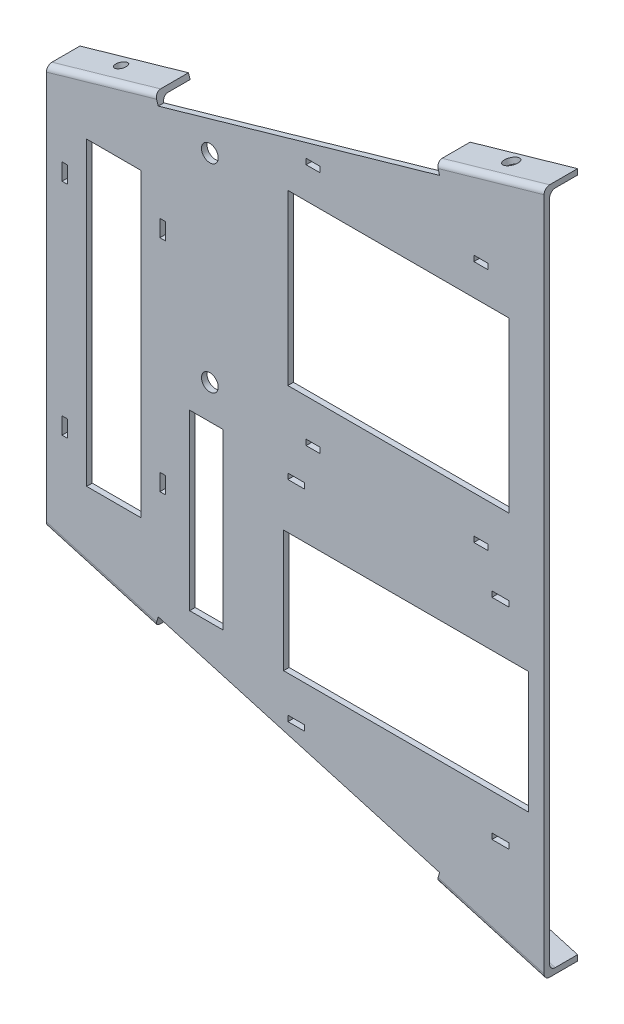
SolidWorks part; units mm, degrees
material "6061 Alloy"
ref_plane "Płaszczyzna XY" through (0, 0, 0) normal (0, 0, 1) x (1, 0, 0)
ref_plane "Płaszczyzna XZ" through (0, 0, 0) normal (0, 1, 0) x (1, 0, 0)
ref_plane "Płaszczyzna YZ" through (0, 0, 0) normal (1, 0, 0) x (0, 0, -1)
sketch "Sketch1" plane through (0, 0, 0) normal (0, 0, 1) x (1, 0, 0)
  line L0 (-10.9048, -82.7238) -> (167.0952, -133.7453) construction
  line L1 (-10.9048, 82.7238) -> (167.0952, 133.7453) construction
  line L2 (-299.5051, 0) -> (299.5051, 0) construction
  line L3 (-10.9048, -69.7204) -> (-10.9048, 69.7204)
  line L4 (167.0952, -120.7419) -> (167.0952, 120.7419)
  line L5 (-10.9048, 69.7204) -> (167.0952, 120.7419)
  line L6 (167.0952, -120.7419) -> (-10.9048, -69.7204)
  point P6 (-10.9048, 0)
extrude "Boss-Extrude1" add sketch "Sketch1" along normal blind 2
sketch "Sketch2" plane through (0, 0, 2) normal (0, 0, 1) x (1, 0, 0)
  line L0 (13.1875, -57.6943) -> (13.1875, 61.3057) construction
  line L1 (29.6875, 38.6369) -> (31.6875, 38.6369)
  line L2 (29.6875, 38.6369) -> (29.6875, 44.6369)
  line L3 (29.6875, 44.6369) -> (31.6875, 44.6369)
  line L4 (29.6875, 32.3057) -> (29.6875, 52.3057) construction
  line L5 (31.6875, 38.6369) -> (31.6875, 44.6369)
  line L6 (-3.3125, 2.3057) -> (29.6875, 2.3057) construction
  line L7 (31.6875, -34.0255) -> (31.6875, -40.0255)
  line L8 (161.9963, 2.39) -> (161.9963, 87.39)
  line L9 (66.9963, 2.39) -> (161.9963, 2.39)
  line L10 (66.9963, 87.39) -> (66.9963, 2.39)
  line L11 (161.9963, 87.39) -> (66.9963, 87.39)
  line L12 (161.9963, 2.39) -> (161.9963, 87.39) construction
  line L13 (66.9963, 2.39) -> (161.9963, 2.39) construction
  line L14 (66.9963, 87.39) -> (66.9963, 2.39) construction
  line L15 (161.9963, 87.39) -> (66.9963, 87.39) construction
  line L16 (161.4673, -13.3702) -> (68.4673, -13.3702)
  line L17 (166.4673, -81.3702) -> (166.4673, -18.3702)
  line L18 (68.4673, -86.3702) -> (161.4673, -86.3702)
  line L19 (63.4673, -18.3702) -> (63.4673, -81.3702)
  line L20 (161.4673, -13.3702) -> (68.4673, -13.3702) construction
  line L21 (166.4673, -81.3702) -> (166.4673, -18.3702) construction
  line L22 (68.4673, -86.3702) -> (161.4673, -86.3702) construction
  line L23 (63.4673, -18.3702) -> (63.4673, -81.3702) construction
  line L24 (-3.3125, 32.3057) -> (-3.3125, -27.6943)
  line L25 (29.6875, 32.3057) -> (-3.3125, 32.3057)
  line L26 (29.6875, -27.6943) -> (29.6875, 32.3057)
  line L27 (-3.3125, -27.6943) -> (29.6875, -27.6943)
  line L28 (-3.3125, 32.3057) -> (-3.3125, -27.6943) construction
  line L29 (29.6875, 32.3057) -> (-3.3125, 32.3057) construction
  line L30 (29.6875, -27.6943) -> (29.6875, 32.3057) construction
  line L31 (-3.3125, -27.6943) -> (29.6875, -27.6943) construction
  line L32 (27.6875, 61.3057) -> (-1.3125, 61.3057)
  line L33 (29.6875, 52.3057) -> (29.6875, 59.3057)
  line L34 (-3.3125, 52.3057) -> (29.6875, 52.3057)
  line L35 (-3.3125, 59.3057) -> (-3.3125, 52.3057)
  line L36 (27.6875, 61.3057) -> (-1.3125, 61.3057) construction
  line L37 (29.6875, 52.3057) -> (29.6875, 59.3057) construction
  line L38 (-3.3125, 52.3057) -> (29.6875, 52.3057) construction
  line L39 (-3.3125, 59.3057) -> (-3.3125, 52.3057) construction
  line L40 (-1.3125, -57.6943) -> (27.6875, -57.6943)
  line L41 (-3.3125, -47.6943) -> (-3.3125, -55.6943)
  line L42 (29.6875, -47.6943) -> (-3.3125, -47.6943)
  line L43 (29.6875, -55.6943) -> (29.6875, -47.6943)
  line L44 (-1.3125, -57.6943) -> (27.6875, -57.6943) construction
  line L45 (-3.3125, -47.6943) -> (-3.3125, -55.6943) construction
  line L46 (29.6875, -47.6943) -> (-3.3125, -47.6943) construction
  line L47 (29.6875, -55.6943) -> (29.6875, -47.6943) construction
  line L48 (29.6875, -34.0255) -> (31.6875, -34.0255)
  line L49 (29.6875, -34.0255) -> (29.6875, -40.0255)
  line L50 (29.6875, -40.0255) -> (31.6875, -40.0255)
  line L51 (-3.3125, 44.6369) -> (-5.3125, 44.6369)
  line L52 (-3.3125, 38.6369) -> (-3.3125, 44.6369)
  line L53 (-3.3125, 38.6369) -> (-5.3125, 38.6369)
  line L54 (-5.3125, 38.6369) -> (-5.3125, 44.6369)
  line L55 (-3.3125, -34.0255) -> (-5.3125, -34.0255)
  line L56 (-5.3125, -34.0255) -> (-5.3125, -40.0255)
  line L57 (-3.3125, -40.0255) -> (-5.3125, -40.0255)
  line L58 (-3.3125, -34.0255) -> (-3.3125, -40.0255)
  line L59 (78.4673, -64.5246) -> (78.4673, -86.3702) construction
  line L60 (3.485, -51.4878) -> (22.8899, -51.4878)
  line L61 (3.485, -51.4878) -> (3.485, 56.0992)
  line L62 (3.485, 56.0992) -> (22.8899, 56.0992)
  line L63 (22.8899, -51.4878) -> (22.8899, 56.0992)
  line L64 (3.485, -51.4878) -> (22.8899, 56.0992) construction
  line L65 (3.485, 56.0992) -> (22.8899, -51.4878) construction
  line L66 (40.3295, -71.5793) -> (52.3295, -71.5793)
  line L67 (40.3295, -71.5793) -> (40.3295, -9.4599)
  line L68 (40.3295, -9.4599) -> (52.3295, -9.4599)
  line L69 (52.3295, -71.5793) -> (52.3295, -9.4599)
  line L70 (40.3295, -71.5793) -> (52.3295, -9.4599) construction
  line L71 (40.3295, -9.4599) -> (52.3295, -71.5793) construction
  line L72 (75.4673, -86.3702) -> (81.4673, -86.3702)
  line L73 (75.4673, -86.3702) -> (75.4673, -88.3702)
  line L74 (75.4673, -88.3702) -> (81.4673, -88.3702)
  line L75 (75.4673, -64.5246) -> (81.4673, -64.5246)
  line L76 (75.4673, -34.5246) -> (75.4673, -64.5246)
  line L77 (81.4673, -34.5246) -> (75.4673, -34.5246)
  line L78 (81.4673, -64.5246) -> (81.4673, -34.5246)
  line L79 (75.4673, -64.5246) -> (81.4673, -64.5246) construction
  line L80 (75.4673, -34.5246) -> (75.4673, -64.5246) construction
  line L81 (81.4673, -34.5246) -> (75.4673, -34.5246) construction
  line L82 (81.4673, -64.5246) -> (81.4673, -34.5246) construction
  line L83 (148.4673, -34.5246) -> (148.4673, -64.5246)
  line L84 (154.4673, -34.5246) -> (148.4673, -34.5246)
  line L85 (154.4673, -64.5246) -> (154.4673, -34.5246)
  line L86 (148.4673, -64.5246) -> (154.4673, -64.5246)
  line L87 (148.4673, -34.5246) -> (148.4673, -64.5246) construction
  line L88 (154.4673, -34.5246) -> (148.4673, -34.5246) construction
  line L89 (154.4673, -64.5246) -> (154.4673, -34.5246) construction
  line L90 (148.4673, -64.5246) -> (154.4673, -64.5246) construction
  line L91 (147.4963, 27.4636) -> (147.4963, 62.3163)
  line L92 (141.4963, 27.4636) -> (147.4963, 27.4636)
  line L93 (141.4963, 62.3163) -> (141.4963, 27.4636)
  line L94 (147.4963, 62.3163) -> (141.4963, 62.3163)
  line L95 (147.4963, 27.4636) -> (147.4963, 62.3163) construction
  line L96 (141.4963, 27.4636) -> (147.4963, 27.4636) construction
  line L97 (141.4963, 62.3163) -> (141.4963, 27.4636) construction
  line L98 (147.4963, 62.3163) -> (141.4963, 62.3163) construction
  line L99 (87.4963, 62.3163) -> (81.4963, 62.3163)
  line L100 (87.4963, 27.4636) -> (87.4963, 62.3163)
  line L101 (81.4963, 27.4636) -> (87.4963, 27.4636)
  line L102 (81.4963, 62.3163) -> (81.4963, 27.4636)
  line L103 (87.4963, 62.3163) -> (81.4963, 62.3163) construction
  line L104 (87.4963, 27.4636) -> (87.4963, 62.3163) construction
  line L105 (81.4963, 27.4636) -> (87.4963, 27.4636) construction
  line L106 (81.4963, 62.3163) -> (81.4963, 27.4636) construction
  line L107 (81.4673, -88.3702) -> (81.4673, -86.3702)
  line L108 (63.4673, -49.8702) -> (166.4673, -49.8702) construction
  line L109 (114.9673, -86.3702) -> (114.9673, -13.3702) construction
  line L110 (75.4673, -13.3702) -> (75.4673, -11.3702)
  line L111 (75.4673, -11.3702) -> (81.4673, -11.3702)
  line L112 (75.4673, -13.3702) -> (81.4673, -13.3702)
  line L113 (81.4673, -11.3702) -> (81.4673, -13.3702)
  line L114 (148.4673, -88.3702) -> (148.4673, -86.3702)
  line L115 (154.4673, -88.3702) -> (148.4673, -88.3702)
  line L116 (154.4673, -86.3702) -> (154.4673, -88.3702)
  line L117 (154.4673, -86.3702) -> (148.4673, -86.3702)
  line L118 (148.4673, -11.3702) -> (148.4673, -13.3702)
  line L119 (154.4673, -13.3702) -> (148.4673, -13.3702)
  line L120 (154.4673, -11.3702) -> (148.4673, -11.3702)
  line L121 (154.4673, -13.3702) -> (154.4673, -11.3702)
  line L122 (86.9963, 0.39) -> (86.9963, 2.39)
  line L123 (86.9963, 0.39) -> (81.9963, 0.39)
  line L124 (86.9963, 2.39) -> (81.9963, 2.39)
  line L125 (81.9963, 0.39) -> (81.9963, 2.39)
  line L126 (86.9963, 0.39) -> (81.9963, 2.39) construction
  line L127 (86.9963, 2.39) -> (81.9963, 0.39) construction
  line L128 (66.9963, 44.89) -> (161.9963, 44.89) construction
  line L129 (114.4963, 2.39) -> (114.4963, 87.39) construction
  line L130 (81.9963, 89.39) -> (81.9963, 87.39)
  line L131 (86.9963, 89.39) -> (81.9963, 89.39)
  line L132 (86.9963, 87.39) -> (81.9963, 87.39)
  line L133 (86.9963, 89.39) -> (86.9963, 87.39)
  line L134 (141.9963, 89.39) -> (141.9963, 87.39)
  line L135 (141.9963, 87.39) -> (146.9963, 87.39)
  line L136 (141.9963, 89.39) -> (146.9963, 89.39)
  line L137 (146.9963, 89.39) -> (146.9963, 87.39)
  line L138 (141.9963, 2.39) -> (146.9963, 0.39) construction
  line L139 (141.9963, 0.39) -> (146.9963, 2.39) construction
  line L140 (146.9963, 0.39) -> (146.9963, 2.39)
  line L141 (141.9963, 2.39) -> (146.9963, 2.39)
  line L142 (141.9963, 0.39) -> (146.9963, 0.39)
  line L143 (141.9963, 0.39) -> (141.9963, 2.39)
  line L144 (-10.9048, 69.7204) -> (-10.9048, -69.7204) construction
  line L146 (73.9192, -73.3653) -> (161.4673, -73.3653)
  line L147 (73.9192, -73.3653) -> (73.9192, -29.7941)
  line L148 (73.9192, -29.7941) -> (161.4673, -29.7941)
  line L149 (161.4673, -73.3653) -> (161.4673, -29.7941)
  line L150 (75.4673, 15.7339) -> (154.4673, 15.7339)
  line L151 (75.4673, 15.7339) -> (75.4673, 76.1907)
  line L152 (75.4673, 76.1907) -> (154.4673, 76.1907)
  line L153 (154.4673, 15.7339) -> (154.4673, 76.1907)
  circle A0 centre (47.5637, 2.7699) radius 3 construction
  circle A1 centre (47.5637, 73.7699) radius 3 construction
  arc A2 (29.6875, 59.3057) -> (27.6875, 61.3057) centre (27.6875, 59.3057) ccw
  arc A3 (-1.3125, 61.3057) -> (-3.3125, 59.3057) centre (-1.3125, 59.3057) ccw
  arc A4 (166.4673, -18.3702) -> (161.4673, -13.3702) centre (161.4673, -18.3702) ccw
  arc A5 (161.4673, -86.3702) -> (166.4673, -81.3702) centre (161.4673, -81.3702) ccw
  arc A6 (63.4673, -81.3702) -> (68.4673, -86.3702) centre (68.4673, -81.3702) ccw
  arc A7 (68.4673, -13.3702) -> (63.4673, -18.3702) centre (68.4673, -18.3702) ccw
  arc A8 (166.4673, -18.3702) -> (161.4673, -13.3702) centre (161.4673, -18.3702) ccw construction
  arc A9 (161.4673, -86.3702) -> (166.4673, -81.3702) centre (161.4673, -81.3702) ccw construction
  arc A10 (63.4673, -81.3702) -> (68.4673, -86.3702) centre (68.4673, -81.3702) ccw construction
  arc A11 (68.4673, -13.3702) -> (63.4673, -18.3702) centre (68.4673, -18.3702) ccw construction
  arc A12 (29.6875, 59.3057) -> (27.6875, 61.3057) centre (27.6875, 59.3057) ccw construction
  arc A13 (-1.3125, 61.3057) -> (-3.3125, 59.3057) centre (-1.3125, 59.3057) ccw construction
  arc A14 (-3.3125, -55.6943) -> (-1.3125, -57.6943) centre (-1.3125, -55.6943) ccw
  arc A15 (27.6875, -57.6943) -> (29.6875, -55.6943) centre (27.6875, -55.6943) ccw
  arc A16 (-3.3125, -55.6943) -> (-1.3125, -57.6943) centre (-1.3125, -55.6943) ccw construction
  arc A17 (27.6875, -57.6943) -> (29.6875, -55.6943) centre (27.6875, -55.6943) ccw construction
  circle A18 centre (47.5637, 2.7699) radius 3
  circle A19 centre (47.5637, 73.7699) radius 3
  point P44 (45.9552, 2.3057)
  point P57 (13.1875, 2.3057)
  point P84 (78.4673, -64.5246)
  point P87 (78.4673, -86.3702)
  point P102 (151.4673, -86.3702)
  point P107 (84.4963, 2.39)
  point P109 (84.4963, 27.4636)
  point P142 (46.3295, -9.4599)
  dimension "D6" = 2
  dimension "D7" = 6
  dimension "D12" = 6
  dimension "D13" = 2
  dimension "D14" = 2
  dimension "D15" = 5
  dimension "D16" = 10.6421
  dimension "D17" = 12
  dimension "D18" = 48.2344
  dimension "D19" = 13.885
  dimension "D1" = 0
  dimension "D2" = 0
  dimension "D3" = 0
  dimension "D4" = 0
  dimension "D5" = 0
  dimension "D8" = 0
  dimension "D9" = 0
  dimension "D10" = 0
  dimension "D11" = 0
extrude "Cut-Extrude1" cut sketch "Sketch2" against normal blind 10
sketch "Sketch3" plane through (0, 0, 0) normal (0, 0, -1) x (-1, 0, 0)
  line L0 (10.9048, -69.7204) -> (-167.0952, -120.7419) construction
  line L1 (10.9048, -69.7204) -> (-167.0952, -120.7419)
  line L2 (10.9048, -69.7204) -> (10.9048, -71.7204)
  line L3 (10.9048, 69.7204) -> (10.9048, -69.7204) construction
  line L4 (-167.0952, -120.7419) -> (-167.0952, -122.7419)
  line L5 (-167.0952, -122.7419) -> (10.9048, -71.7204)
  line L6 (-167.0952, -120.7419) -> (-167.0952, 120.7419) construction
  line L7 (1.1, 0) -> (-1.1, 0) construction
  line L8 (-167.0952, 120.7419) -> (-167.0952, 122.7419)
  line L9 (-167.0952, 122.7419) -> (10.9048, 71.7204)
  line L10 (10.9048, 69.7204) -> (10.9048, 71.7204)
  line L11 (10.9048, 69.7204) -> (-167.0952, 120.7419)
  dimension "D1" = 2
  dimension "D2" = 2
extrude "Boss-Extrude2" add sketch "Sketch3" along normal blind 10 and the other way blind 2
fillet "Fillet1" radius 2 4 edges at (78.0952, 95.2312, 0) (78.0952, -95.2312, 0) (78.0952, -97.2312, 2) (78.0952, 97.2312, 2)
sketch "Sketch4" plane through (0, 0, 0) normal (0, 0, -1) x (-1, 0, 0)
  line L0 (10.9048, 67.6399) -> (-167.0952, 118.6614) construction
  line L1 (-29.0952, 79.1054) -> (-127.0952, 107.1959)
  line L3 (-124.8909, 114.8862) -> (-26.8909, 86.1054)
  line L4 (-26.8909, 86.1054) -> (-29.0952, 79.1054)
  line L5 (10.9048, 67.6399) -> (10.9048, -67.6399) construction
  line L11 (-128.0926, 113.6428) -> (-128.6437, 111.7203) construction
  line L12 (-128.0926, 113.6428) -> (-128.6437, 111.7203)
  line L13 (-128.6437, 111.7203) -> (-129.7245, 107.9495)
  line L14 (-127.0952, 107.1959) -> (-129.7245, 107.9495)
  line L15 (-124.8909, 114.8862) -> (-127.5153, 115.6569)
  line L16 (-128.0926, 113.6428) -> (-127.5153, 115.6569)
  line L18 (6.6, 0) -> (-6.6, 0) construction
  line L19 (-127.0952, -107.1959) -> (-129.7245, -107.9495)
  line L20 (-128.6437, -111.7203) -> (-129.7245, -107.9495)
  line L21 (-128.0926, -113.6428) -> (-128.6437, -111.7203)
  line L22 (-128.0926, -113.6428) -> (-127.5153, -115.6569)
  line L23 (-124.8909, -114.8862) -> (-127.5153, -115.6569)
  line L24 (-124.8909, -114.8862) -> (-26.8909, -86.1054)
  line L25 (-29.0952, -79.1054) -> (-127.0952, -107.1959)
  line L26 (-26.8909, -86.1054) -> (-29.0952, -79.1054)
  dimension "D1" = 40
  dimension "D2" = 40
  dimension "D3" = 8
  dimension "D4" = 7
  dimension "D5" = 179.628
  dimension "D6" = 271.113
extrude "Cut-Extrude2" cut sketch "Sketch4" against normal blind 10 and the other way blind 10
sketch "Sketch5" plane through (-19.2951, -67.3154, 0) normal (0.2755, 0.9613, 0) x (0.9613, -0.2755, 0)
  line L0 (154.4473, 10) -> (193.8963, 10) construction
  line L1 (193.8963, 2) -> (193.8963, 10) construction
  line L2 (8.7282, 10) -> (49.7139, 10) construction
  line L3 (8.7282, 2) -> (8.7282, 10) construction
  circle A0 centre (173.8963, 6) radius 2.5
  circle A1 centre (28.7282, 6) radius 2
  dimension "D1" = 5
  dimension "D6" = 4
  dimension "D2" = 4
  dimension "D3" = 20
  dimension "D4" = 4
  dimension "D5" = 20
extrude "Cut-Extrude3" cut sketch "Sketch5" against normal blind 10
mirror "Mirror1" about plane through (0, 0, 0) normal (0, 1, 0) of "Cut-Extrude3"
